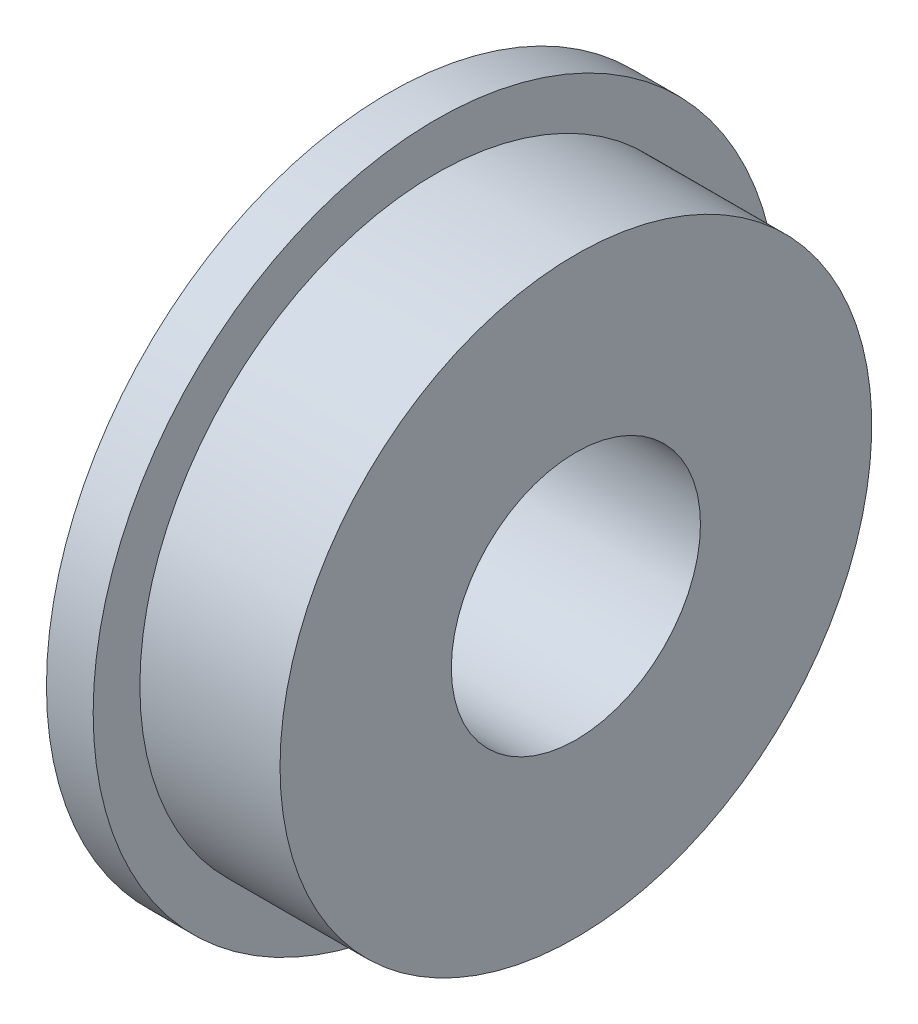
SolidWorks part; units mm, degrees
ref_plane "Front" through (0, 0, 0) normal (0, 0, 1) x (1, 0, 0)
ref_plane "Top" through (0, 0, 0) normal (0, 1, 0) x (1, 0, 0)
ref_plane "Right" through (0, 0, 0) normal (1, 0, 0) x (0, 0, -1)
ref_plane "Plane1" through (0, 0, 0) normal (0, 0, -1) x (-1, 0, 0)
sketch "Sketch1" plane through (0, 0, 0) normal (0, 0, -1) x (-1, 0, 0)
  line L0 (-1.5, 9.5) -> (-6, 9.5)
  line L1 (-6, 9.5) -> (-6, 4)
  line L2 (-6, 4) -> (0, 4)
  line L3 (0, 4) -> (0, 11)
  line L4 (0, 11) -> (-1.5, 11)
  line L5 (-1.5, 11) -> (-1.5, 9.5)
  line L6 (-6, 0) -> (0, 0) construction
revolve "Revolve1" add sketch "Sketch1" angle 360 about L6 reverse direction yes
